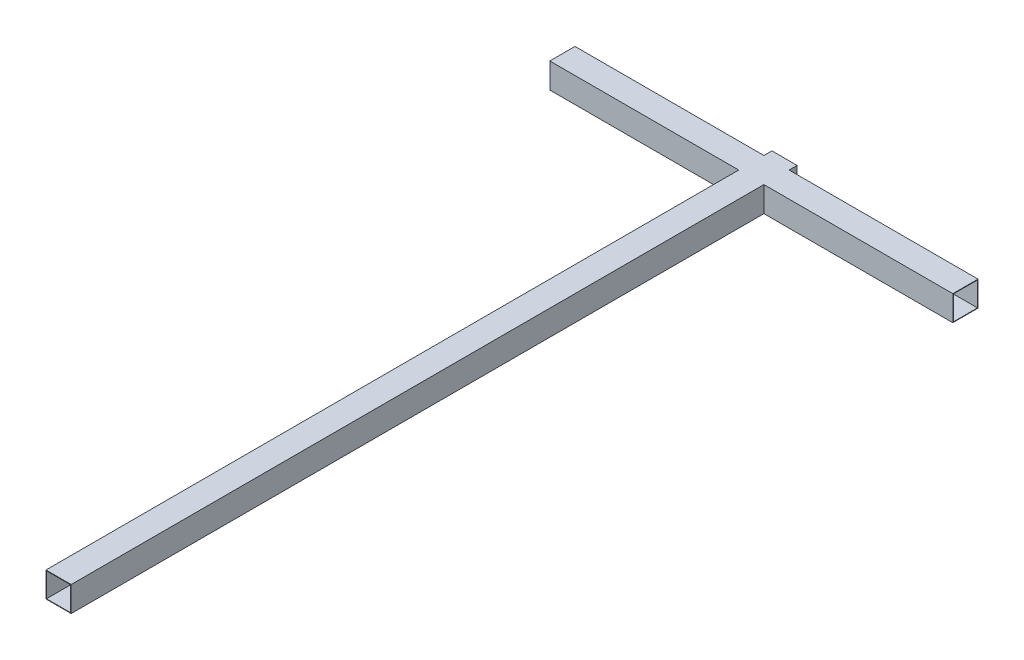
SolidWorks part; units mm, degrees
ref_plane "Front Plane" through (0, 0, 0) normal (0, 0, 1) x (1, 0, 0)
ref_plane "Top Plane" through (0, 0, 0) normal (0, 1, 0) x (1, 0, 0)
ref_plane "Right Plane" through (0, 0, 0) normal (1, 0, 0) x (0, 0, -1)
ref_plane "GROUND-WL" through (0, 0, 0) normal (0, 1, 0) x (1, 0, 0)
ref_plane "CL-BL" through (0, 0, 0) normal (1, 0, 0) x (0, 0, -1)
ref_plane "WHEEL-RAD-WL" through (0, 100, 0) normal (0, 1, 0) x (1, 0, 0)
ref_plane "FRAME-WL" through (0, 250, 0) normal (0, 1, 0) x (1, 0, 0)
ref_plane "REAR-WHEEL-STA" through (0, 0, 0) normal (0, 0, 1) x (1, 0, 0)
ref_plane "FRONT-WHEEL-STA" through (0, 0, 1200) normal (0, 0, 1) x (1, 0, 0)
ref_plane "LEFT-WHEEL-BL" through (400, 0, 0) normal (1, 0, 0) x (0, 0, -1)
ref_plane "RIGHT-WHEEL-BL" through (-400, 0, 0) normal (1, 0, 0) x (0, 0, -1)
ref_plane "REAR-FRAME-BEAM-STA" through (0, 0, -100) normal (0, 0, 1) x (1, 0, 0)
ref_axis "REAR-WHEEL-AXIS" through (88.99, 100, 0) along (-1, 0, 0)
ref_axis "FRONT-WHEEL-AXIS" through (-88.99, 100, 1200) along (1, 0, 0)
sketch "frame-sketch" plane through (0, 250, 0) normal (0, 1, 0) x (1, 0, 0)
  line L0 (-400, 100) -> (400, 100)
  line L1 (0, -1300) -> (0, 140.9199)
  line L2 (280, 100) -> (0, -180)
  line L3 (-280, 100) -> (0, -180)
  line L4 (0, -55) -> (0, 55) construction
  line L6 (-55, 100) -> (55, 100) construction
  line L7 (400, -55) -> (400, 55) construction
  line L8 (-400, -55) -> (-400, 55) construction
  line L9 (-55, -1200) -> (55, -1200) construction
  point P7 (0, 0)
  point P12 (0, 0)
  point P15 (0, 0)
  point P18 (0, -1896.6111)
  point P19 (0, 0)
  point P22 (0, 0)
  point P23 (-283.2419, 18.3431)
  point P24 (-251.919, 37.1666)
  point P25 (0, 0)
  dimension "D1" = 45
  dimension "D2" = 100
  dimension "D3" = 45
  dimension "D4" = 280
  dimension "D5" = 800
sketch "front-wheel-sketch" plane through (0, 0, 0) normal (1, 0, 0) x (0, 0, -1)
  circle A0 centre (-1200, 100) radius 100
  point P2 (0, 0)
  dimension "D1" = 200
sketch "rear-left-wheel-sketch" plane through (400, 0, 0) normal (1, 0, 0) x (0, 0, -1)
  circle A0 centre (0, 100) radius 100
  point P3 (76.1917, 106.3784)
  dimension "D1" = 200
sketch "rear-right-wheel-sketch" plane through (-400, 0, 0) normal (1, 0, 0) x (0, 0, -1)
  circle A0 centre (0, 100) radius 100
  dimension "D1" = 200
sketch "fwd-aft-beam-xs" plane through (0, 0, 0) normal (0, 0, 1) x (1, 0, 0)
  line L1 (-25, 225) -> (25, 225)
  line L2 (-25, 225) -> (-25, 275)
  line L3 (-25, 275) -> (25, 275)
  line L4 (25, 225) -> (25, 275)
  line L5 (-25, 225) -> (25, 275) construction
  line L6 (-25, 275) -> (25, 225) construction
  line L7 (-24, 226) -> (24, 226)
  line L8 (-24, 226) -> (-24, 274)
  line L9 (-24, 274) -> (24, 274)
  line L10 (24, 226) -> (24, 274)
  line L11 (-24, 226) -> (24, 274) construction
  line L12 (-24, 274) -> (24, 226) construction
  point P0 (0, 250)
  point P7 (0, 250)
  dimension "D1" = 50
  dimension "D2" = 50
  dimension "D3" = 1
sketch "fwd-aft-beam-profile" plane through (0, 250, -250) normal (0, -1, 0) x (1, 0, 0)
  line L1 (0, 1550) -> (0, 109.0801) construction
  line L2 (0, 1550) -> (0, 109.0801)
sketch "lat-beam-xs" plane through (0, 0, 0) normal (1, 0, 0) x (0, 0, -1)
  line L1 (75, 225) -> (125, 225)
  line L2 (75, 225) -> (75, 275)
  line L3 (75, 275) -> (125, 275)
  line L4 (125, 225) -> (125, 275)
  line L5 (75, 225) -> (125, 275) construction
  line L6 (75, 275) -> (125, 225) construction
  line L7 (76, 226) -> (124, 226)
  line L8 (76, 226) -> (76, 274)
  line L9 (76, 274) -> (124, 274)
  line L10 (124, 226) -> (124, 274)
  line L11 (76, 226) -> (124, 274) construction
  line L12 (76, 274) -> (124, 226) construction
  point P0 (100, 250)
  point P5 (100, 250)
  point P10 (0, 0)
  point P11 (0, 0)
  dimension "D1" = 50
  dimension "D2" = 50
  dimension "D3" = 1
sketch "lat-beam-profile" plane through (0, 250, 0) normal (0, 1, 0) x (1, 0, 0)
  line L0 (-400, 100) -> (400, 100) construction
  line L1 (-400, 100) -> (400, 100)
sweep "fwd-aft-beam" add profiles "fwd-aft-beam-xs" path "fwd-aft-beam-profile"
sweep "lat-beam" add profiles "lat-beam-xs" path "lat-beam-profile"
equation "\"wheel_rad\"= 100"
equation "\"clearance_wheel_frame\"= 50"
equation "\"D1@WHEEL-RAD-WL\" = \"wheel_rad\""
equation "\"D1@FRAME-WL\" = 2 * \"wheel_rad\" + \"clearance_wheel_frame\""
equation "\"rear_wheel_separation\"= 800"
equation "\"front_wheel_offset\" = 1200"
equation "\"D1@FRONT-WHEEL-STA\" = \"front_wheel_offset\""
equation "\"D1@LEFT-WHEEL-BL\" = \"rear_wheel_separation\" / 2"
equation "\"D1@RIGHT-WHEEL-BL\" = \"rear_wheel_separation\" / 2"
equation "\"rear_frame_beam_offset\"= 100"
equation "\"D1@REAR-FRAME-BEAM-STA\"=\"rear_frame_beam_offset\""
equation "\"fwd_beam_overshoot\"= 100"
equation "\"D2@frame-sketch\" = \"fwd_beam_overshoot\""
equation "\"D3@frame-sketch\" = \"D1@frame-sketch\""
equation "\"D4@frame-sketch\" = .7 * \"D5@frame-sketch\" / 2"
equation "\"wheel_width\"= 30"
equation "\"D1@front-wheel-sketch\" = \"wheel_rad\" * 2"
equation "\"D1@rear-left-wheel-sketch\" = \"wheel_rad\" * 2"
equation "\"D1@rear-right-wheel-sketch\" = \"wheel_rad\" * 2"
equation "\"frame_xs_edge\"= 50"
equation "\"D1@fwd-aft-beam-xs\" = \"frame_xs_edge\""
equation "\"D2@fwd-aft-beam-xs\" = \"D1@fwd-aft-beam-xs\""
equation "\"D1@lat-beam-xs\" = \"frame_xs_edge\""
equation "\"D2@lat-beam-xs\" = \"D1@lat-beam-xs\""
